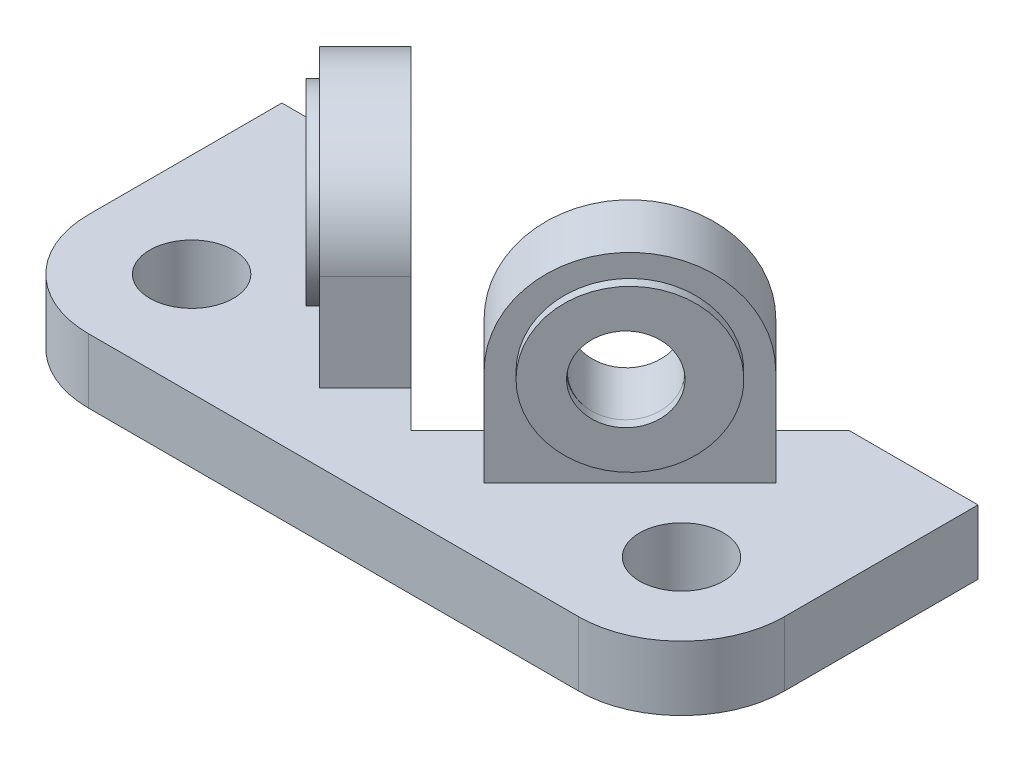
SolidWorks part; units mm, degrees
ref_plane "Front Plane" through (0, 0, 0) normal (0, 0, 1) x (1, 0, 0)
ref_plane "Top Plane" through (0, 0, 0) normal (0, 1, 0) x (1, 0, 0)
ref_plane "Right Plane" through (0, 0, 0) normal (1, 0, 0) x (0, 0, -1)
sketch "Sketch1" plane through (0, 0, 0) normal (0, 1, 0) x (1, 0, 0)
  line L0 (0, 0) -> (0, 80.2555) construction
  line L1 (-108, 68) -> (-108, 8)
  line L2 (-76, -24) -> (-0.6208, -24)
  line L3 (0, 0) -> (-68, 68)
  line L4 (-68, 68) -> (-108, 68)
  line L5 (0, 0) -> (68, 68)
  line L6 (76, -24) -> (-0.6208, -24)
  line L7 (108, 68) -> (108, 8)
  line L8 (68, 68) -> (108, 68)
  line L9 (-56.6274, 56.6274) -> (-11.3726, 11.3726)
  line L10 (-56.6274, 56.6274) -> (-70.7696, 42.4853)
  line L11 (-11.3726, 11.3726) -> (-25.5147, -2.7696)
  line L12 (-70.7696, 42.4853) -> (-25.5147, -2.7696)
  line L13 (-70.7696, 42.4853) -> (-68, 68) construction
  line L14 (-25.5147, -2.7696) -> (0, 0) construction
  line L15 (11.3726, 11.3726) -> (25.5147, -2.7696)
  line L16 (70.7696, 42.4853) -> (25.5147, -2.7696)
  line L17 (56.6274, 56.6274) -> (70.7696, 42.4853)
  line L18 (56.6274, 56.6274) -> (11.3726, 11.3726)
  arc A0 (-76, -24) -> (-108, 8) centre (-76, 8) cw
  arc A1 (76, -24) -> (108, 8) centre (76, 8) ccw
  circle A2 centre (-76, 8) radius 13
  circle A3 centre (76, 8) radius 13
  dimension "D2" = 32
  dimension "D6" = 26
  dimension "D1" = 45
  dimension "D3" = 40
  dimension "D4" = 92
  dimension "D5" = 108
  dimension "D7" = 20
  dimension "D8" = 64
extrude "Boss-Extrude1" add sketch "Sketch1" along normal blind 20 contours L6 A1 L7 L8 L5 L17 L16 L15 L3 L11 L12 L10 L4 L1 A0 L2 A2 A3 region at (-88, 0, -65.6522)
extrude "Boss-Extrude2" add sketch "Sketch1<3>" along normal blind 82 contours L10 L12 L11 L3 region at (-41.0711, 0, -26.9289)
sketch "Sketch1<3>" plane through (0, 0, 0) normal (0, 1, 0) x (1, 0, 0) same geometry as "Sketch1"
fillet "Fillet1" 2 edges at (-18.4437, 82, -4.3015) (-63.6985, 82, -49.5563) type full round first side face at (-18.4437, 51, -4.3015) second side face at (-63.6985, 51, -49.5563) middle face at (-41.0711, 82, -26.9289)
sketch "Sketch3" plane through (-14.1421, 0, 14.1421) normal (-0.7071, 0, 0.7071) x (0.7071, 0, 0.7071)
  line L0 (-80.0833, 50) -> (-16.0833, 50) construction
  circle A0 centre (-48.0833, 50) radius 25
  circle A1 centre (-47.1656, 50) radius 13
  dimension "D1" = 26
  dimension "D2" = 50
extrude "Boss-Extrude3" add sketch "Sketch3" along normal blind 3
extrude "Cut-Extrude2" cut sketch "Sketch3<3>" against normal through all contours L0 A1 | A1 L0 region at (-47.4932, 44.4826, -19.209) region at (-47.4932, 55.5174, -19.209)
sketch "Sketch3<3>" plane through (-14.1421, 0, 14.1421) normal (-0.7071, 0, 0.7071) x (0.7071, 0, 0.7071) same geometry as "Sketch3"
ref_plane "Plane1" through (0, 0, 0) normal (1, 0, 0) x (0, 0, -1)
mirror "Mirror1" about plane through (0, 0, 0) normal (1, 0, 0) of "Boss-Extrude3", "Boss-Extrude2", "Fillet1"
sketch "Sketch5" plane through (14.1421, 0, 14.1421) normal (0.7071, 0, 0.7071) x (0.7071, 0, -0.7071)
  circle A0 centre (47.3403, 49.8329) radius 13
  dimension "D1" = 26
extrude "Cut-Extrude3" cut sketch "Sketch5" against normal through all
